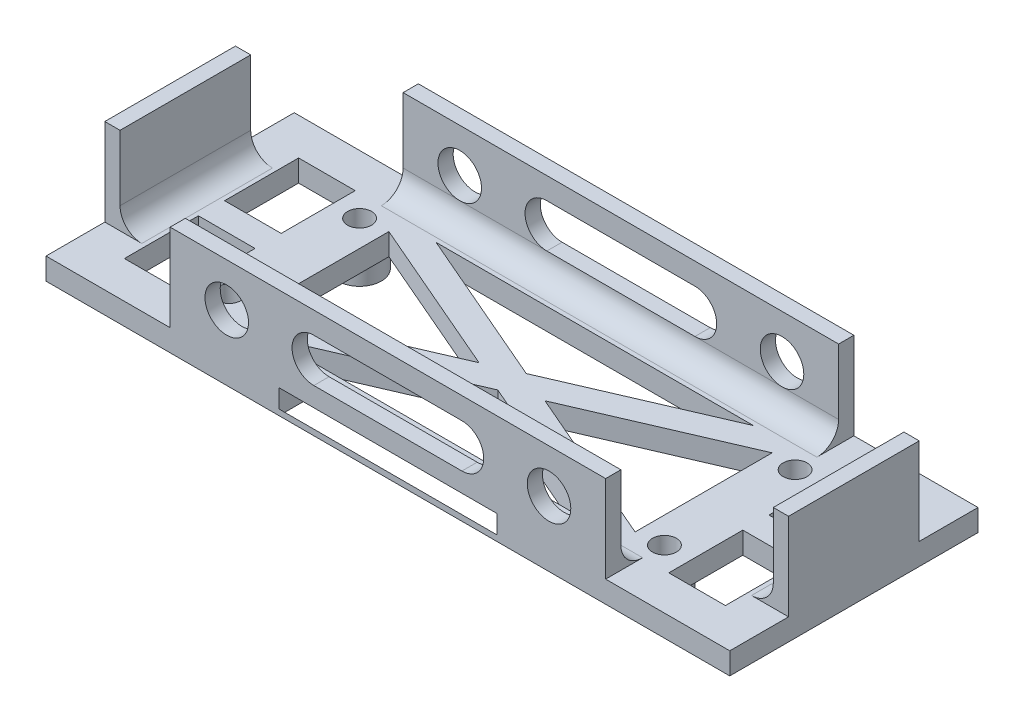
SolidWorks part; units mm, degrees
material "打印件"
ref_plane "前视基准面" through (0, 0, 0) normal (0, 0, 1) x (1, 0, 0)
ref_plane "上视基准面" through (0, 0, 0) normal (0, 1, 0) x (1, 0, 0)
ref_plane "右视基准面" through (0, 0, 0) normal (1, 0, 0) x (0, 0, -1)
sketch "草图1" plane through (0, 0, 0) normal (0, 1, 0) x (1, 0, 0)
  line L1 (0, 0) -> (160, 0)
  line L2 (0, 0) -> (0, 64)
  line L3 (0, 64) -> (160, 64)
  line L4 (160, 0) -> (160, 64)
  line L5 (0, 0) -> (160, 64) construction
  line L6 (0, 64) -> (160, 0) construction
  point P4 (80, 32)
  dimension "D1" = 160
  dimension "D2" = 64
extrude "凸台-拉伸1" add sketch "草图1" along normal blind 5
sketch "草图2" plane through (0, 5, 0) normal (0, 1, 0) x (1, 0, 0)
  line L0 (160, 64) -> (0, 64) construction
  line L1 (30, 64) -> (130, 64)
  line L2 (30, 64) -> (30, 57)
  line L3 (30, 57) -> (130, 57)
  line L4 (130, 64) -> (130, 57)
  line L5 (30, 64) -> (130, 57) construction
  line L6 (30, 57) -> (130, 64) construction
  line L7 (160, 0) -> (160, 64) construction
  line L8 (160, 47) -> (155, 47)
  line L9 (160, 47) -> (160, 17)
  line L10 (160, 17) -> (155, 17)
  line L11 (155, 47) -> (155, 17)
  line L12 (160, 47) -> (155, 17) construction
  line L13 (160, 17) -> (155, 47) construction
  line L14 (0, 64) -> (0, 0) construction
  line L15 (0, 47) -> (5, 47)
  line L16 (0, 47) -> (0, 17)
  line L17 (0, 17) -> (5, 17)
  line L18 (5, 47) -> (5, 17)
  line L19 (0, 47) -> (5, 17) construction
  line L20 (0, 17) -> (5, 47) construction
  line L21 (0, 0) -> (160, 0) construction
  line L23 (30, 0) -> (130, 0)
  line L24 (30, 0) -> (30, 7)
  line L25 (30, 7) -> (130, 7)
  line L26 (130, 0) -> (130, 7)
  line L27 (30, 0) -> (130, 7) construction
  line L28 (30, 7) -> (130, 0) construction
  point P4 (80, 60.5)
  point P11 (157.5, 32)
  point P18 (2.5, 32)
  point P27 (80, 3.5)
  dimension "D2" = 100
  dimension "D3" = 30
  dimension "D4" = 5
  dimension "D5" = 30
  dimension "D6" = 17
  dimension "D7" = 5
  dimension "D8" = 30
  dimension "D9" = 17
  dimension "D10" = 50
  dimension "D11" = 100
  dimension "D12" = 30
  dimension "D13" = 7
extrude "凸台-拉伸2" add sketch "草图2" along normal blind 20
fillet "圆角1" radius 5 4 edges at (80, 5, -7) (5, 5, -32) (155, 5, -32) (80, 5, -57)
sketch "草图3" plane through (0, 0, 0) normal (0, -1, 0) x (1, 0, 0)
  line L0 (160, 0) -> (160, -64) construction
  line L1 (160, -64) -> (0, -64) construction
  circle A0 centre (130, -17) radius 5
  circle A1 centre (130, -47) radius 5
  circle A2 centre (30, -47) radius 5
  circle A3 centre (30, -17) radius 5
  circle A4 centre (130, -47) radius 1.7
  circle A5 centre (130, -17) radius 1.7
  circle A6 centre (30, -17) radius 1.7
  circle A7 centre (30, -47) radius 1.7
  dimension "D1" = 10
  dimension "D2" = 10
  dimension "D3" = 10
  dimension "D4" = 10
  dimension "D6" = 30
  dimension "D7" = 100
  dimension "D8" = 100
  dimension "D9" = 30
  dimension "D10" = 17
  dimension "D11" = 17
  dimension "D12" = 30
  dimension "D13" = 3.4
  dimension "D14" = 3.4
  dimension "D15" = 3.4
  dimension "D16" = 3.4
  dimension "D5" = 30
extrude "凸台-拉伸3" add sketch "草图3" along normal blind 5
sketch "草图4" plane through (0, 5, 0) normal (0, 1, 0) x (1, 0, 0)
  circle A0 centre (130, 17) radius 2.75
  circle A1 centre (130, 47) radius 2.75
  circle A2 centre (30, 17) radius 2.75
  circle A3 centre (30, 47) radius 2.75
  dimension "D1" = 5.5
  dimension "D2" = 5.5
  dimension "D3" = 5.5
  dimension "D4" = 5.5
extrude "切除-拉伸1" cut sketch "草图4" against normal blind 5
sketch "草图5" plane through (0, 25, 0) normal (0, 1, 0) x (1, 0, 0)
  line L0 (160, 47) -> (160, 64) construction
  line L5 (0, 64) -> (160, 64)
  line L6 (0, 64) -> (0, 62)
  line L7 (0, 62) -> (160, 62)
  line L8 (160, 64) -> (160, 62)
  line L9 (0, 64) -> (160, 62) construction
  line L10 (0, 62) -> (160, 64) construction
  line L11 (0, 17) -> (0, 0) construction
  line L12 (160, 0) -> (0, 0)
  line L13 (160, 0) -> (160, 2)
  line L14 (160, 2) -> (0, 2)
  line L15 (0, 0) -> (0, 2)
  line L16 (160, 0) -> (0, 2) construction
  line L17 (160, 2) -> (0, 0) construction
  point P4 (80, 63)
  point P12 (80, 1)
  dimension "D1" = 2
  dimension "D2" = 2
extrude "切除-拉伸2" cut sketch "草图5" against normal blind 64
sketch "草图6" plane through (0, 0, 0) normal (0, -1, 0) x (1, 0, 0)
  line L0 (30, -57) -> (130, -57) construction
  line L1 (43.5674, -51) -> (116.4326, -51)
  line L2 (36, -47.7322) -> (36, -16.2678)
  line L3 (43.5674, -13) -> (116.4326, -13)
  line L4 (124, -47.7322) -> (124, -16.2678)
  line L7 (30, -12) -> (130, -12) construction
  line L8 (116.4326, -51) -> (80, -35.2678)
  line L9 (43.5674, -13) -> (80, -28.7322)
  line L10 (43.5674, -51) -> (80, -35.2678)
  line L11 (116.4326, -13) -> (80, -28.7322)
  line L12 (87.5674, -32) -> (124, -16.2678)
  line L15 (72.4326, -32) -> (36, -47.7322)
  line L16 (72.4326, -32) -> (36, -16.2678)
  line L17 (87.5674, -32) -> (124, -47.7322)
  circle A0 centre (30, -47) radius 5 construction
  circle A1 centre (130, -47) radius 5 construction
  point P4 (80, -32)
  dimension "D3" = 6
  dimension "D4" = 6
  dimension "D1" = 6
  dimension "D2" = 1
  dimension "D5" = 6
  dimension "D6" = 6
extrude "切除-拉伸3" cut sketch "草图6" against normal blind 7
sketch "草图7" plane through (0, 5, 0) normal (0, 1, 0) x (1, 0, 0)
  line L0 (150, 17) -> (150, 47) construction
  line L1 (11, 52) -> (24, 52)
  line L2 (11, 52) -> (11, 35)
  line L3 (11, 12) -> (24, 12)
  line L4 (24, 52) -> (24, 35)
  line L5 (11, 52) -> (16.525, 35) construction
  line L6 (11, 12) -> (17.5, 32) construction
  line L7 (136, 52) -> (149, 52)
  line L8 (136, 52) -> (136, 35)
  line L9 (136, 12) -> (149, 12)
  line L10 (149, 52) -> (149, 35)
  line L11 (136, 52) -> (141.525, 35) construction
  line L12 (136, 12) -> (142.5, 32) construction
  line L13 (10, 47) -> (10, 17) construction
  line L14 (30, 62) -> (0, 62) construction
  line L15 (0, 2) -> (30, 2) construction
  line L16 (160, 62) -> (130, 62) construction
  line L17 (130, 2) -> (160, 2) construction
  line L18 (24, 35) -> (11, 35)
  line L19 (11, 29) -> (24, 29)
  line L20 (24, 29) -> (24, 12)
  line L21 (18.475, 35) -> (24, 52) construction
  line L22 (17.5, 32) -> (24, 12) construction
  line L23 (11, 29) -> (11, 12)
  line L24 (149, 35) -> (136, 35)
  line L25 (136, 29) -> (149, 29)
  line L26 (136, 29) -> (136, 12)
  line L27 (142.5, 32) -> (149, 12) construction
  line L28 (143.475, 35) -> (149, 52) construction
  line L29 (149, 29) -> (149, 12)
  circle A0 centre (130, 47) radius 2.75 construction
  circle A1 centre (30, 47) radius 2.75 construction
  point P4 (17.5, 32)
  point P9 (142.5, 32)
  dimension "D1" = 1
  dimension "D2" = 6
  dimension "D3" = 1
  dimension "D4" = 6
  dimension "D5" = 10
  dimension "D6" = 10
  dimension "D7" = 10
  dimension "D8" = 10
  dimension "D10" = 3
extrude "切除-拉伸4" cut sketch "草图7" against normal blind 7
sketch "草图8" plane through (0, 0, -2) normal (0, 0, 1) x (1, 0, 0)
  line L0 (30, 5) -> (30, 25) construction
  line L1 (130, 25) -> (130, 5) construction
  line L2 (30, 25) -> (130, 25) construction
  line L3 (63, 20) -> (97, 20)
  line L4 (97, 10) -> (63, 10)
  circle A0 centre (43, 15) radius 5
  arc A1 (63, 20) -> (63, 10) centre (63, 15) ccw
  arc A3 (97, 10) -> (97, 20) centre (97, 15) ccw
  circle A4 centre (117, 15) radius 5
  dimension "D1" = 10
  dimension "D2" = 10
  dimension "D4" = 10
  dimension "D5" = 10
  dimension "D6" = 13
  dimension "D7" = 20
  dimension "D8" = 13
  dimension "D9" = 20
  dimension "D11" = 10
  dimension "D12" = 10
  dimension "D14" = 10
  dimension "D15" = 10
extrude "切除-拉伸5" cut sketch "草图8" against normal blind 67
sketch "草图9" plane through (160, 0, 0) normal (1, 0, 0) x (0, 0, -1)
  line L0 (2, 4.4167) -> (2.5833, 5)
  line L1 (2, 0) -> (2, 5) construction
  line L2 (2, 5) -> (17, 5) construction
  line L3 (2.5833, 5) -> (2, 5)
  line L4 (2, 5) -> (2, 4.4167)
  dimension "D1" = 45
extrude "切除-拉伸6" cut sketch "草图9" against normal blind 1
sketch "草图10" plane through (0, 1.2084, 1.2084) normal (0, 0.7071, 0.7071) x (1, 0, 0)
  line L0 (0, 1.4142) -> (160, 1.4142) construction
  line L1 (55, 6.4142) -> (105, 6.4142)
  line L2 (55, 6.4142) -> (55, 3.4142)
  line L3 (55, 3.4142) -> (105, 3.4142)
  line L4 (105, 6.4142) -> (105, 3.4142)
  line L5 (55, 6.4142) -> (105, 3.4142) construction
  line L6 (55, 3.4142) -> (105, 6.4142) construction
  line L7 (130, 4.9497) -> (130, 12.0208) construction
  point P4 (80, 4.9142)
  dimension "D1" = 2
  dimension "D2" = 3
  dimension "D3" = 25
  dimension "D4" = 50
extrude "切除-拉伸7" cut sketch "草图10" against normal blind 9 and the other way blind 15
ref_plane "基准面1" through (0, 0, -32) normal (0, 0, 1) x (1, 0, 0)
mirror "镜向1" about plane through (0, 0, -32) normal (0, 0, 1) of "切除-拉伸7"
sketch "草图12" plane through (0, 0, 0) normal (0, -1, 0) x (1, 0, 0)
  line L0 (0, -62) -> (0, -2) construction
  line L1 (160, -2) -> (0, -2)
  line L2 (160, -2) -> (160, -3.5)
  line L3 (160, -3.5) -> (0, -3.5)
  line L4 (0, -2) -> (0, -3.5)
  line L5 (160, -2) -> (0, -3.5) construction
  line L6 (160, -3.5) -> (0, -2) construction
  line L8 (160, -62) -> (0, -62)
  line L9 (160, -62) -> (160, -60.5)
  line L10 (160, -60.5) -> (0, -60.5)
  line L11 (0, -62) -> (0, -60.5)
  line L12 (160, -62) -> (0, -60.5) construction
  line L13 (160, -60.5) -> (0, -62) construction
  point P4 (80, -2.75)
  point P12 (80, -61.25)
  dimension "D1" = 1.5
  dimension "D2" = 1.5
extrude "切除-拉伸11" cut sketch "草图12" against normal blind 34
sketch "草图13" plane through (0, 0, 0) normal (0, -1, 0) x (1, 0, 0)
  line L0 (0, -3.5) -> (160, -3.5) construction
  line L1 (160, -60.5) -> (158.5, -60.5)
  line L2 (160, -60.5) -> (160, -3.5)
  line L3 (160, -3.5) -> (158.5, -3.5)
  line L4 (158.5, -60.5) -> (158.5, -3.5)
  line L5 (160, -60.5) -> (158.5, -3.5) construction
  line L6 (160, -3.5) -> (158.5, -60.5) construction
  line L8 (0, -60.5) -> (1.5, -60.5)
  line L9 (0, -60.5) -> (0, -3.5)
  line L10 (0, -3.5) -> (1.5, -3.5)
  line L11 (1.5, -60.5) -> (1.5, -3.5)
  line L12 (0, -60.5) -> (1.5, -3.5) construction
  line L13 (0, -3.5) -> (1.5, -60.5) construction
  point P4 (159.25, -32)
  point P12 (0.75, -32)
  dimension "D1" = 1.5
  dimension "D2" = 1.5
extrude "切除-拉伸12" cut sketch "草图13" against normal blind 34
fillet "圆角2" radius 1 4 edges at (130, 0, -22) (130, 0, -52) (30, 0, -52) (30, 0, -22)
